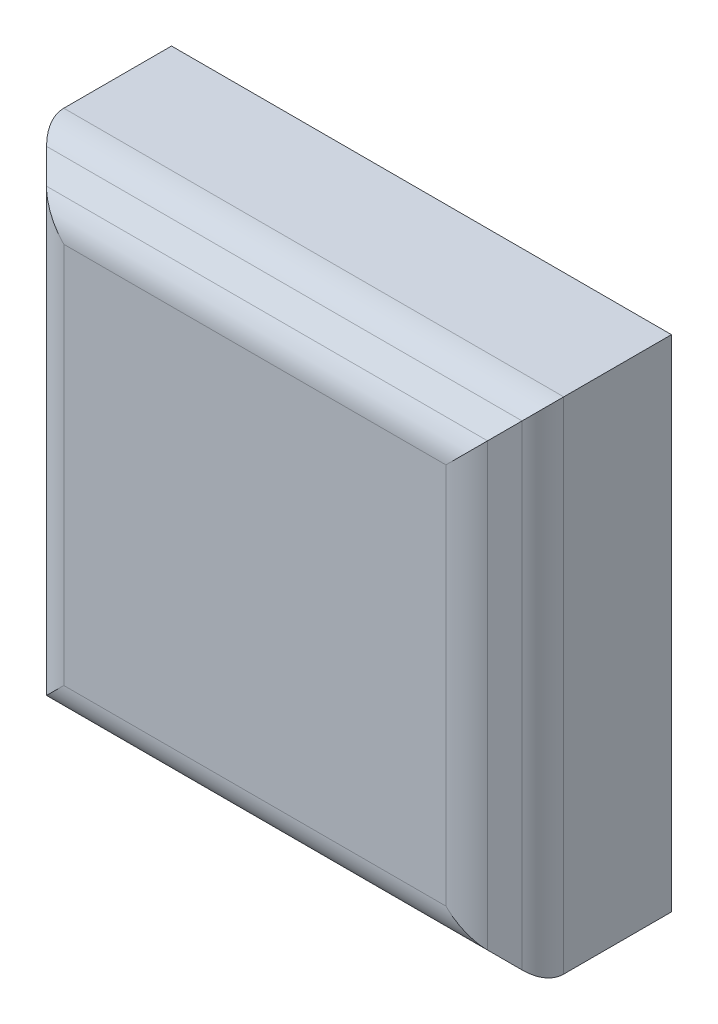
SolidWorks part; units mm, degrees
ref_plane "Front" through (0, 0, 0) normal (0, 0, 1) x (1, 0, 0)
ref_plane "Top" through (0, 0, 0) normal (0, 1, 0) x (1, 0, 0)
ref_plane "Right" through (0, 0, 0) normal (1, 0, 0) x (0, 0, -1)
sketch "Sketch1" plane through (0, 0, 0) normal (0, 0, 1) x (1, 0, 0)
  line L1 (-36.4889, 115.9437) -> (83.5111, 115.9437)
  line L2 (-36.4889, 115.9437) -> (-36.4889, -4.0563)
  line L3 (-36.4889, -4.0563) -> (83.5111, -4.0563)
  line L4 (83.5111, 115.9437) -> (83.5111, -4.0563)
  dimension "D1" = 120
  dimension "D2" = 120
extrude "Boss-Extrude1" add sketch "Sketch1" along normal blind 40
chamfer "Chamfer1" distance 10 angle 45 4 edges at (23.5111, -4.0563, 40) (83.5111, 55.9437, 40) (23.5111, 115.9437, 40) (-36.4889, 55.9437, 40)
fillet "Fillet1" radius 10 8 edges at (83.5111, 55.9437, 30) (-26.4889, 55.9437, 40) (73.5111, 55.9437, 40) (23.5111, 5.9437, 40) (23.5111, -4.0563, 30) (-36.4889, 55.9437, 30) (23.5111, 115.9437, 30) (23.5111, 105.9437, 40)
shell "Shell1" thickness 10 removed face at (23.5111, 55.9437, 0)
